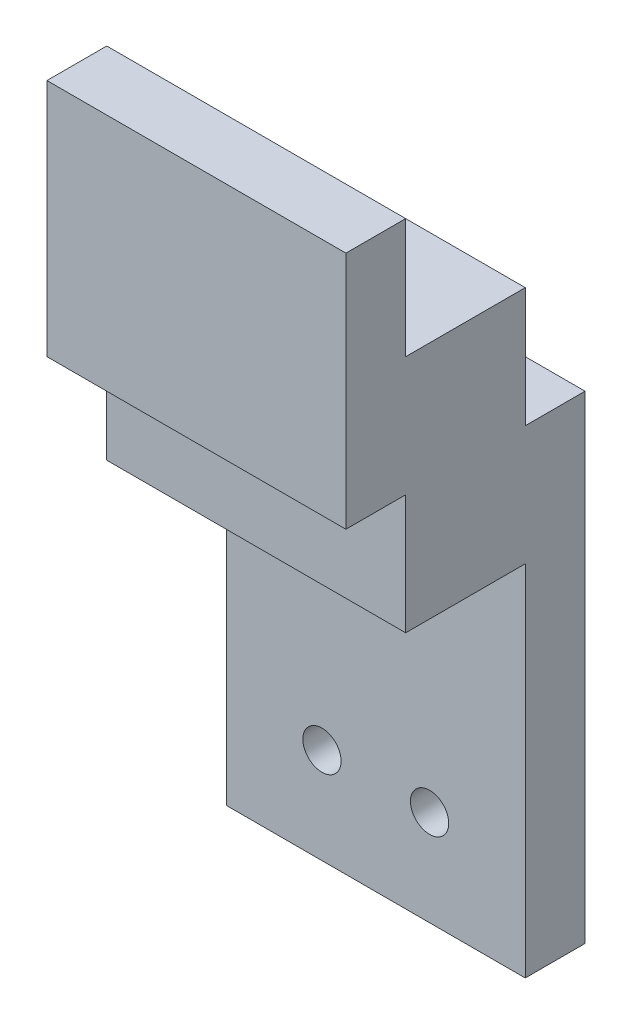
SolidWorks part; units mm, degrees
ref_plane "前视基准面" through (0, 0, 0) normal (0, 0, 1) x (1, 0, 0)
ref_plane "上视基准面" through (0, 0, 0) normal (0, 1, 0) x (1, 0, 0)
ref_plane "右视基准面" through (0, 0, 0) normal (1, 0, 0) x (0, 0, -1)
other "Configuration Table"
sketch "草图1" plane through (0, 0, 0) normal (0, 0, 1) x (1, 0, 0)
  line L1 (0, 0) -> (25, 0)
  line L2 (0, 0) -> (0, 40)
  line L3 (0, 40) -> (25, 40)
  line L4 (25, 0) -> (25, 40)
  circle A0 centre (8, 8) radius 1.6
  circle A1 centre (17, 8) radius 1.6
  dimension "D2" = 8
  dimension "D3" = 8
  dimension "D5" = 8
  dimension "D6" = 3.2
  dimension "D7" = 3.2
  dimension "D1" = 25
  dimension "D4" = 8
  dimension "D8" = 40
extrude "凸台-拉伸1" add sketch "草图1" along normal blind 5
sketch "草图3" plane through (0, 0, 5) normal (0, 0, 1) x (1, 0, 0)
  line L0 (25, 0) -> (25, 40) construction
  line L5 (25, 30) -> (0, 30)
  line L6 (25, 30) -> (25, 50)
  line L7 (25, 50) -> (0, 50)
  line L8 (0, 30) -> (0, 50)
  line L9 (25, 40) -> (0, 40) construction
  dimension "D1" = 10
  dimension "D2" = 20
extrude "凸台-拉伸2" add sketch "草图3" along normal blind 10
sketch "草图4" plane through (0, 0, 15) normal (0, 0, 1) x (1, 0, 0)
  line L0 (0, 50) -> (0, 30) construction
  line L1 (0, 40) -> (25, 40)
  line L2 (0, 40) -> (0, 60)
  line L3 (0, 60) -> (25, 60)
  line L4 (25, 40) -> (25, 60)
  line L5 (25, 50) -> (0, 50) construction
  dimension "D1" = 10
  dimension "D2" = 20
extrude "凸台-拉伸3" add sketch "草图4" along normal blind 5
